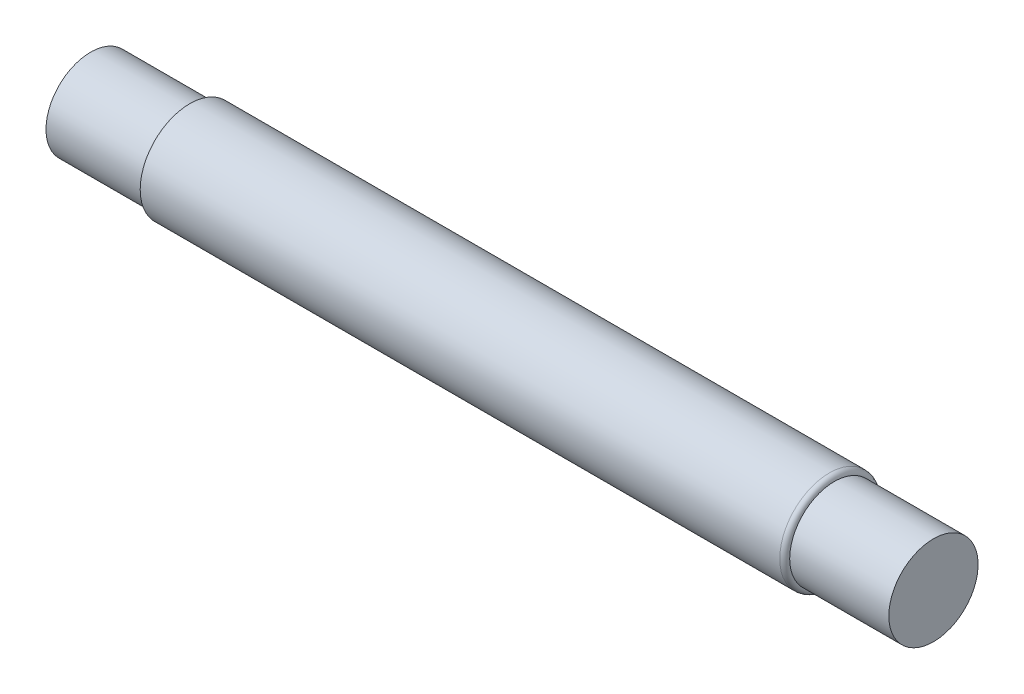
SolidWorks part; units mm, degrees
ref_plane "前视基准面" through (0, 0, 0) normal (0, 0, 1) x (1, 0, 0)
ref_plane "上视基准面" through (0, 0, 0) normal (0, 1, 0) x (1, 0, 0)
ref_plane "右视基准面" through (0, 0, 0) normal (1, 0, 0) x (0, 0, -1)
other "Configuration Table"
sketch "草图8" plane through (0, 0, 0) normal (0, 0, 1) x (1, 0, 0)
  line L0 (0, 0) -> (340, 0)
  line L1 (340, 0) -> (340, 18)
  line L2 (340, 18) -> (300, 18)
  line L3 (300, 18) -> (300, 20)
  line L4 (300, 20) -> (40, 20)
  line L5 (40, 20) -> (40, 18)
  line L6 (40, 18) -> (0, 18)
  line L7 (0, 18) -> (0, 0)
  line L8 (0, 0) -> (340, 0) construction
revolve "旋转1" add sketch "草图8" angle 360 about L8
fillet "圆角1" radius 2 1 edges at (300, 0, 20) tangent propagation no
